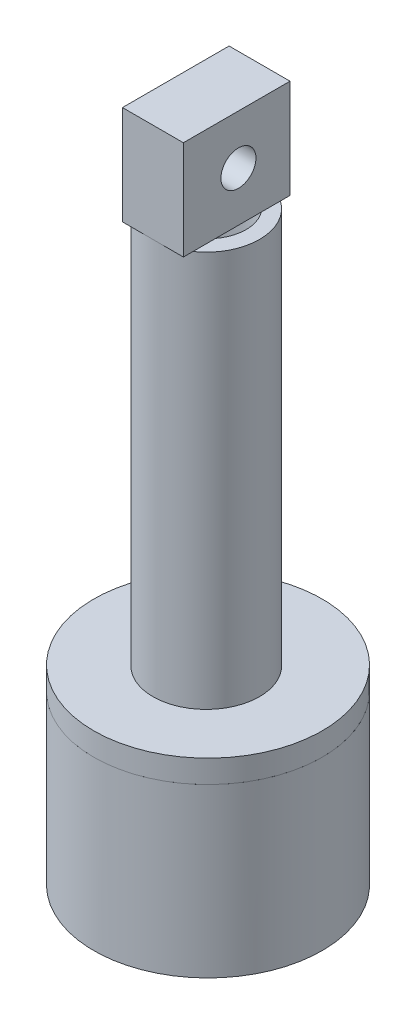
SolidWorks part; units mm, degrees
ref_plane "Front Plane" through (0, 0, 0) normal (0, 0, 1) x (1, 0, 0)
ref_plane "Top Plane" through (0, 0, 0) normal (0, 1, 0) x (1, 0, 0)
ref_plane "Right Plane" through (0, 0, 0) normal (1, 0, 0) x (0, 0, -1)
sketch "Sketch1" plane through (0, 0, 0) normal (0, 1, 0) x (1, 0, 0)
  circle A0 centre (0, 0) radius 15
  circle A1 centre (0, 0) radius 12.5
  dimension "D1" = 30
  dimension "D2" = 25
extrude "Boss-Extrude1" add sketch "Sketch1" along normal blind 20
sketch "Sketch2" plane through (0, 0, 0) normal (0, -1, 0) x (1, 0, 0)
  circle A0 centre (0, 0) radius 15
  circle A1 centre (0, 0) radius 11
  circle M1 centre (0, 0) radius 15
  circle M2 centre (0, 0) radius 12.5
  dimension "D1" = 22
extrude "Boss-Extrude2" add sketch "Sketch2" along normal blind 2 contours M1 M2 | A1 M2 region at (-14.5757, 0, 0) region at (-12.1464, 0, 0)
sketch "Sketch4" plane through (0, 20, 0) normal (0, 1, 0) x (1, 0, 0)
  circle A0 centre (0, 0) radius 15
extrude "Boss-Extrude3" add sketch "Sketch4" along normal blind 3 separate body
sketch "Sketch5" plane through (0, 0, 0) normal (1, 0, 0) x (0, 0, -1)
  line L0 (15, 23) -> (-15, 23) construction
  line L1 (-7.2309, 75) -> (6.7691, 75)
  line L2 (-0.2309, 23) -> (6.7691, 23)
  line L4 (-7.2309, 88) -> (6.7691, 88)
  line L5 (6.7691, 23) -> (6.7691, 88)
  line L6 (-0.2309, 23) -> (-0.2309, 25) construction
  line L7 (-7.2309, 75) -> (-7.2309, 88)
  line L8 (-0.2309, 23) -> (-0.2309, 25)
  line L9 (-0.2309, 73) -> (4.7691, 73)
  line L10 (4.7691, 73) -> (4.7691, 25)
  line L11 (4.7691, 25) -> (-0.2309, 25)
  line L12 (-0.2309, 73) -> (-0.2309, 99.3203) construction
  line L13 (-0.2309, 73) -> (-0.2309, 75)
  point P0 (-0.5375, 23)
  dimension "D1" = 2
  dimension "D2" = 52
  dimension "D3" = 2
  dimension "D4" = 2
  dimension "D5" = 7
revolve "Revolve1" add sketch "Sketch5" angle 360 about L12 region at (0, 49, -5.2046)
extrude "Boss-Extrude4" add sketch "Sketch5<6>" along normal mid plane 8 contours L7 L1 L5 L4 region at (0, 81.5, 0.2309)
sketch "Sketch5<6>" plane through (0, 0, 0) normal (1, 0, 0) x (0, 0, -1) same geometry as "Sketch5"
sketch "Sketch7" plane through (4, 0, 0) normal (1, 0, 0) x (0, 0, -1)
  line L0 (6.7691, 75) -> (6.7691, 88) construction
  circle A0 centre (0, 81.5) radius 2.3
  point P0 (6.7691, 81.5)
  point P3 (0, 81.5)
  dimension "D1" = 4.6
extrude "Cut-Extrude1" cut sketch "Sketch7" against normal blind 10
sketch "Sketch8" plane through (0, 75, 0) normal (0, 1, 0) x (1, 0, 0)
  circle A0 centre (0, 0) radius 5
  dimension "D1" = 10
extrude "Cut-Extrude2" cut sketch "Sketch8" against normal blind 10
